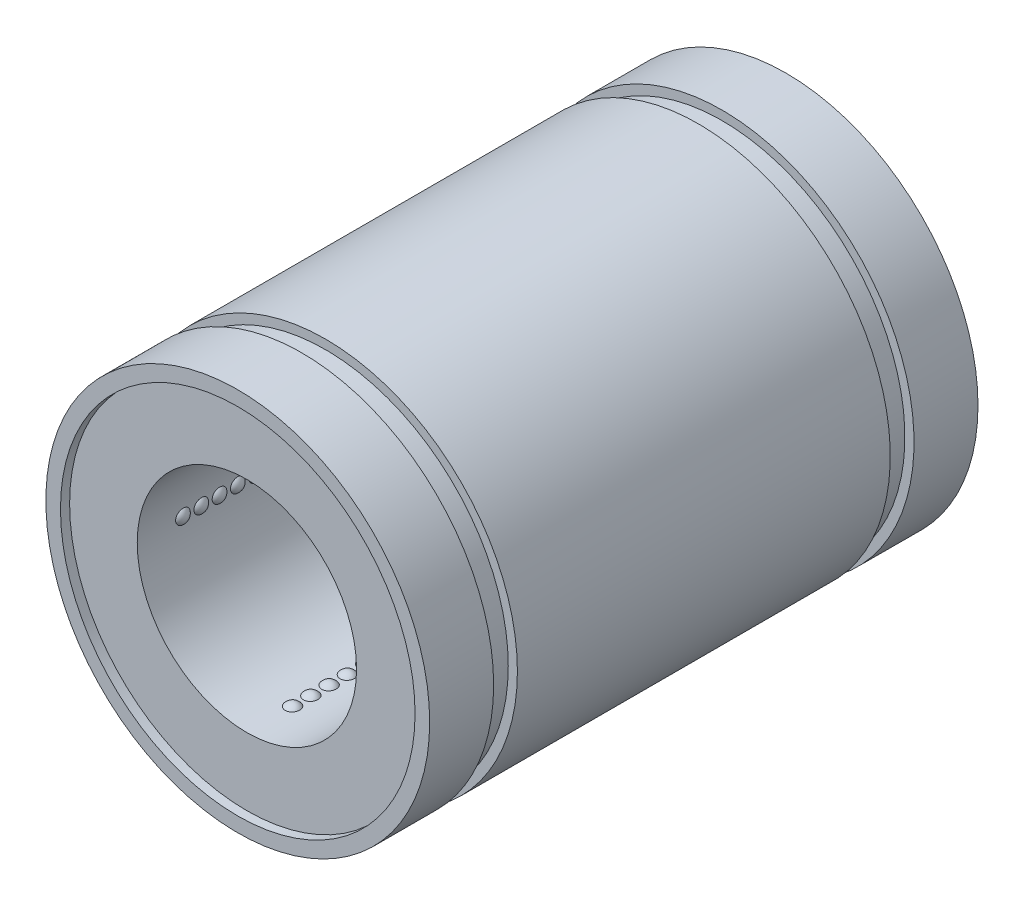
SolidWorks part; units mm, degrees
note: '?' marks a value the reader was unsure of.
ref_plane "Front Plane" through (0, 0, 0) normal (0, 0, 1) x (1, 0, 0)
ref_plane "Top Plane" through (0, 0, 0) normal (0, 1, 0) x (1, 0, 0)
ref_plane "Right Plane" through (0, 0, 0) normal (1, 0, 0) x (0, 0, -1)
sketch "Sketch1" plane through (0, 0, 0) normal (0, 0, 1) x (1, 0, 0)
  circle A0 centre (0, 0) radius 6
  circle A1 centre (0, 0) radius 10.5
  dimension "D1" = 12
  dimension "D2" = 21
extrude "Boss-Extrude1" add sketch "Sketch1" along normal blind 30
sketch "Sketch2" plane through (0, 0, 30) normal (0, 0, 1) x (1, 0, 0)
  circle A0 centre (0, 0) radius 6
  circle A1 centre (0, 0) radius 9.7
  circle A2 centre (0, 0) radius 10.5 construction
  dimension "D1" = 0.8
extrude "Cut-Extrude1" cut sketch "Sketch2" against normal blind 0.5
sketch "Sketch3" plane through (0, 0, 0) normal (0, 0, -1) x (-1, 0, 0)
  circle A0 centre (0, 0) radius 6
  circle A1 centre (0, 0) radius 9.7
  circle A2 centre (0, 0) radius 10.5 construction
  dimension "D1" = 0.8
extrude "Cut-Extrude2" cut sketch "Sketch3" against normal blind 0.5
ref_plane "Plane1" through (0, 0, 27) normal (0, 0, 1) x (1, 0, 0)
sketch "Sketch4" plane through (0, 0, 27) normal (0, 0, 1) x (1, 0, 0)
  line L0 (0, -6.3) -> (0, -5.8) construction
  line L1 (0, -6.3) -> (0, -6.8) construction
  line L2 (0, -5.8) -> (0, -6.8)
  arc A2 (0, -6.8) -> (0, -5.8) centre (0, -6.3) ccw
  circle A3 centre (0, 0) radius 6 construction
  dimension "D1" = 1
  dimension "D2" = 6.3
revolve "Revolve1" add sketch "Sketch4" angle 360 about L2
ref_axis "Axis1" through (0, 0, 29.5) along (0, 0, -1)?
pattern_linear "LPattern1" count 25 spacing 1 along (0, 0, -1) of "Revolve1"
pattern_circular "CirPattern1" count 4 over 360 about axis through (0, 0, 0) along (0, 0, 1) of "LPattern1", "Revolve1"
ref_plane "Plane2" through (0, 0, 3.5) normal (0, 0, -1) x (-1, 0, 0)
sketch "Sketch5" plane through (0, 0, 3.5) normal (0, 0, -1) x (-1, 0, 0)
  circle A0 centre (0, 0) radius 10
  circle A1 centre (0, 0) radius 11.6256
  dimension "D1" = 20
extrude "Cut-Extrude3" cut sketch "Sketch5" against normal blind 1.3
ref_plane "Plane3" through (0, 0, 26.5) normal (0, 0, 1) x (1, 0, 0)
sketch "Sketch6" plane through (0, 0, 26.5) normal (0, 0, 1) x (1, 0, 0)
  circle A0 centre (0, 0) radius 10
  circle A1 centre (0, 0) radius 11.732
  dimension "D1" = 20
extrude "Cut-Extrude4" cut sketch "Sketch6" against normal blind 1.3
equation "\"l\"=360"
